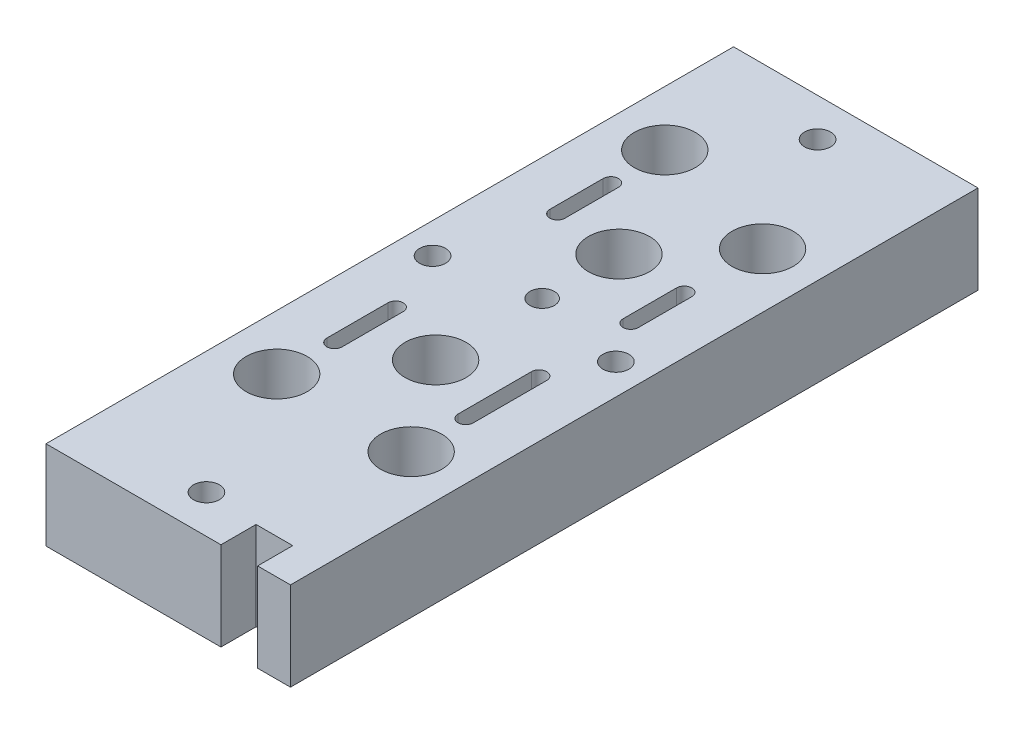
SolidWorks part; units mm, degrees
material "Plain Carbon Steel"
ref_plane "Front Plane" through (0, 0, 0) normal (0, 0, 1) x (1, 0, 0)
ref_plane "Top Plane" through (0, 0, 0) normal (0, 1, 0) x (1, 0, 0)
ref_plane "Right Plane" through (0, 0, 0) normal (1, 0, 0) x (0, 0, -1)
sketch "Sketch1" plane through (0, 0, 0) normal (0, 1, 0) x (1, 0, 0)
  line L1 (-40, -112.5) -> (40, -112.5)
  line L2 (-40, -112.5) -> (-40, 112.5)
  line L3 (-40, 112.5) -> (40, 112.5)
  line L4 (40, -112.5) -> (40, 112.5)
  line L5 (-40, -112.5) -> (40, 112.5) construction
  line L6 (-40, 112.5) -> (40, -112.5) construction
  point P0 (0, 0)
  dimension "D1" = 225
  dimension "D2" = 80
extrude "Boss-Extrude1" add sketch "Sketch1" against normal blind 29
sketch "Sketch2" plane through (0, 0, 0) normal (0, 1, 0) x (1, 0, 0)
  line L0 (-19, 36.36) -> (-19, 53.86) construction
  line L1 (-24, 53.86) -> (-24, 36.36) construction
  line L2 (-19, -36.59) -> (-19, -16.59) construction
  line L3 (-24, -16.59) -> (-24, -36.59) construction
  line L4 (24, 17.36) -> (24, 34.86) construction
  line L5 (19, 34.86) -> (19, 17.36) construction
  line L8 (24, -36.64) -> (24, -12.64) construction
  line L9 (19, -12.64) -> (19, -36.64) construction
  line L11 (-19, 36.36) -> (-19, 53.86)
  line L14 (-24, 53.86) -> (-24, 36.36)
  line L15 (-19, -36.59) -> (-19, -16.59)
  line L16 (-24, -16.59) -> (-24, -36.59)
  line L17 (24, 17.36) -> (24, 34.86)
  line L20 (19, 34.86) -> (19, 17.36)
  line L21 (24, -36.64) -> (24, -12.64)
  line L23 (19, -12.64) -> (19, -36.64)
  arc A0 (-24, 36.36) -> (-19, 36.36) centre (-21.5, 36.36) ccw construction
  arc A1 (-19, 53.86) -> (-24, 53.86) centre (-21.5, 53.86) ccw construction
  arc A2 (-24, -36.59) -> (-19, -36.59) centre (-21.5, -36.59) ccw construction
  arc A3 (-19, -16.59) -> (-24, -16.59) centre (-21.5, -16.59) ccw construction
  arc A4 (19, 17.36) -> (24, 17.36) centre (21.5, 17.36) ccw construction
  arc A5 (24, 34.86) -> (19, 34.86) centre (21.5, 34.86) ccw construction
  arc A8 (19, -36.64) -> (24, -36.64) centre (21.5, -36.64) ccw construction
  arc A9 (24, -12.64) -> (19, -12.64) centre (21.5, -12.64) ccw construction
  arc A14 (-24, 36.36) -> (-19, 36.36) centre (-21.5, 36.36) ccw
  arc A15 (-19, 53.86) -> (-24, 53.86) centre (-21.5, 53.86) ccw
  arc A16 (-24, -36.59) -> (-19, -36.59) centre (-21.5, -36.59) ccw
  arc A17 (-19, -16.59) -> (-24, -16.59) centre (-21.5, -16.59) ccw
  arc A20 (19, 17.36) -> (24, 17.36) centre (21.5, 17.36) ccw
  arc A21 (24, 34.86) -> (19, 34.86) centre (21.5, 34.86) ccw
  arc A26 (19, -36.64) -> (24, -36.64) centre (21.5, -36.64) ccw
  arc A27 (24, -12.64) -> (19, -12.64) centre (21.5, -12.64) ccw
extrude "Cut-Extrude1" cut sketch "Sketch2" against normal up to next
sketch "Sketch4" plane through (0, 0, 0) normal (0, 1, 0) x (1, 0, 0)
  circle A0 centre (-22, 72) radius 10
  circle A1 centre (22, 60) radius 10
  circle A2 centre (0, 35) radius 10
  circle A3 centre (0, -25) radius 10
  circle A4 centre (22, -55) radius 10
  circle A5 centre (-22, -55) radius 10
  dimension "D1" = 20
extrude "Cut-Extrude2" cut sketch "Sketch4" against normal blind 20
sketch "Sketch5" plane through (0, -29, 0) normal (0, -1, 0) x (1, 0, 0)
  circle A0 centre (0, 100) radius 8.5
  circle A1 centre (0, -100) radius 8.5
  dimension "D1" = 17
extrude "Cut-Extrude3" cut sketch "Sketch5" against normal blind 5
sketch "Sketch6" plane through (0, 0, 0) normal (0, 1, 0) x (1, 0, 0)
  line L0 (-40, -112.5) -> (40, -112.5) construction
  line L1 (17.25, -112.5) -> (29.25, -112.5)
  line L2 (17.25, -112.5) -> (17.25, -101)
  line L3 (17.25, -101) -> (29.25, -101)
  line L4 (29.25, -112.5) -> (29.25, -101)
  line L5 (28.25, -102.5) -> (28.25, -115) construction
  line L6 (18.25, -115) -> (18.25, -102.5) construction
  line L7 (18.75, -102) -> (27.75, -102) construction
  point P8 (28.25, -108.75)
  point P11 (18.25, -108.75)
  dimension "D1" = 1
  dimension "D2" = 1
  dimension "D3" = 1
extrude "Cut-Extrude4" cut sketch "Sketch6" against normal up to next
hole_wizard "M10 Tapped Hole1" positions "Sketch11" profile "Sketch8" tap size "M10" standard "ISO" end condition through all
sketch "Sketch11" plane through (0, 0, 0) normal (0, 1, 0) x (1, 0, 0)
  circle A0 centre (0, -100) radius 8.5 construction
  circle A1 centre (0, 100) radius 8.5 construction
  point P0 (0, -100)
  point P2 (30, 4)
  point P4 (-30, 4)
  point P6 (0, 100)
  dimension "D3" = 4
  dimension "D4" = 30
  dimension "D5" = 30
sketch "Sketch8" plane through (0, 0, 100) normal (1, 0, 0) x (0, 0, 1)
  line L0 (0, 0) -> (0, 29)
  line L1 (0, 29) -> (4.25, 29)
  line L2 (4.25, 29) -> (4.25, 0)
  line L5 (4.25, 0) -> (0, 0)
  line L11 (0, -6.35) -> (0, 107.95) construction
  dimension "Thru Tap Drill Dia." = 8.5
  dimension "Thru Tap Drill Depth" = 29
cosmetic thread "Hole Thread1" parameters "D2"=10
cosmetic thread "Hole Thread2" parameters "D2"=10
cosmetic thread "Hole Thread3" parameters "D2"=10
cosmetic thread "Hole Thread4" parameters "D2"=10
sketch "Sketch10" plane through (0, 0, 0) normal (0, 1, 0) x (1, 0, 0)
  circle A0 centre (0, 9.86) radius 5 construction
  circle A1 centre (0, 9.86) radius 5 construction
  circle A2 centre (0, 9.86) radius 4
  dimension "D1" = 8
extrude "Cut-Extrude5" cut sketch "Sketch10" against normal up to next
